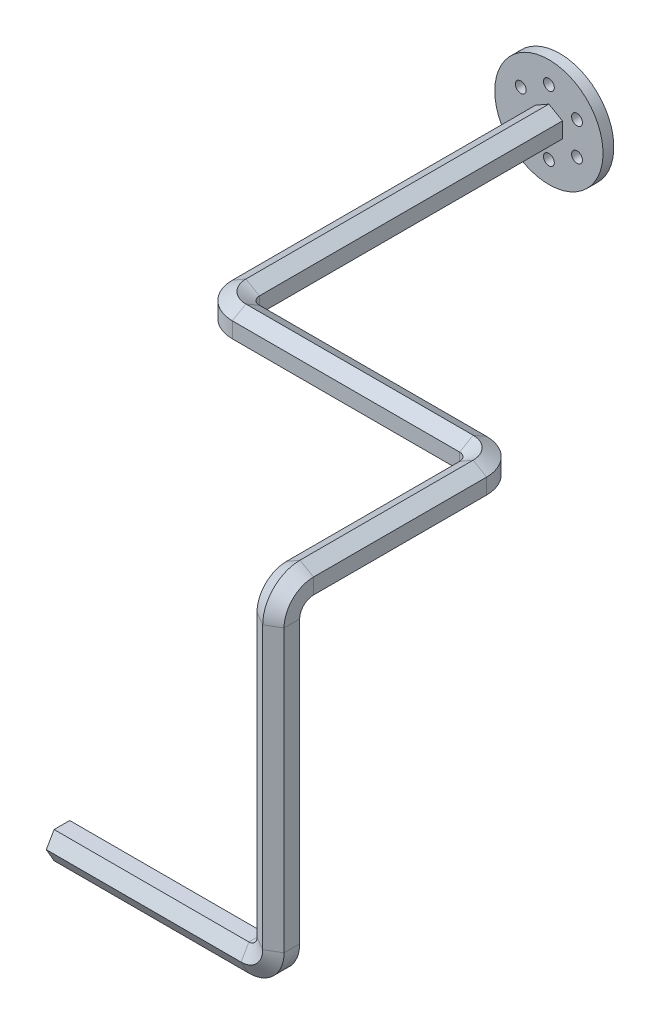
SolidWorks part; units mm, degrees
ref_plane "Front Plane" through (0, 0, 0) normal (0, 0, 1) x (1, 0, 0)
ref_plane "Top Plane" through (0, 0, 0) normal (0, 1, 0) x (1, 0, 0)
ref_plane "Right Plane" through (0, 0, 0) normal (1, 0, 0) x (0, 0, -1)
sketch3d "3DSketch1"
  line L0 (0, 0, 0) -> (180, 0, 0)
  line L1 (200, 20, 0) -> (200, 280, 0)
  line L2 (200, 300, -20) -> (200, 300, -180)
  line L3 (180, 300, -200) -> (-30, 300, -200)
  line L4 (-50, 300, -220) -> (-50, 300, -500)
  arc A0 (-30, 300, -200) -> (-50, 300, -220) centre (-30, 300, -220) ccw
  arc A1 (200, 300, -180) -> (180, 300, -200) centre (180, 300, -180) ccw
  arc A2 (200, 280, 0) -> (200, 300, -20) centre (200, 280, -20) ccw
  arc A3 (180, 0, 0) -> (200, 20, 0) centre (180, 20, 0) ccw
  point P11 (-50, 300, -200)
  point P12 (-30, 280, -220)
  point P15 (200, 300, -200)
  point P16 (180, 320, -180)
  point P19 (200, 300, 0)
  point P20 (180, 280, -20)
  point P23 (200, 0, 0)
  point P24 (180, 20, 20)
  dimension "D6" = 20
  dimension "D1" = 200
  dimension "D2" = 300
  dimension "D3" = 200
  dimension "D4" = 250
  dimension "D5" = 300
sketch "Sketch1" plane through (0, 0, 0) normal (1, 0, 0) x (0, 0, -1)
  line L1 (7.2169, -12.5) -> (14.4338, 0)
  line L2 (14.4338, 0) -> (7.2169, 12.5)
  line L3 (7.2169, 12.5) -> (-7.2169, 12.5)
  line L4 (-7.2169, 12.5) -> (-14.4338, 0)
  line L5 (-14.4338, 0) -> (-7.2169, -12.5)
  line L6 (-7.2169, -12.5) -> (7.2169, -12.5)
  circle A0 centre (0, 0) radius 12.5 construction
  dimension "D1" = 25
sweep "Sweep1" add profiles "Sketch1" path "3DSketch1"
sketch "Sketch2" plane through (0, 0, -500) normal (0, 0, -1) x (-1, 0, 0)
  line L0 (37.5, 307.2169) -> (37.5, 292.7831) construction
  circle A0 centre (50, 300) radius 10
  circle A1 centre (50, 300) radius 50
  circle A2 centre (50, 330) radius 5
  circle A3 centre (75.9808, 315) radius 5
  circle A4 centre (75.9808, 285) radius 5
  circle A5 centre (50, 270) radius 5
  circle A6 centre (24.0192, 285) radius 5
  circle A7 centre (24.0192, 315) radius 5
  point P6 (37.5, 300)
  point P21 (50, 300)
  dimension "D1" = 20
  dimension "D2" = 100
  dimension "D4" = 10
  dimension "D6" = 30
  dimension "D3" = 30
  dimension "D5" = 6
extrude "Boss-Extrude1" add sketch "Sketch2" along normal blind 10
shell "Shell1" thickness 1 removed face at (-60, 300, -500) removed face at (0, 0, 0)
